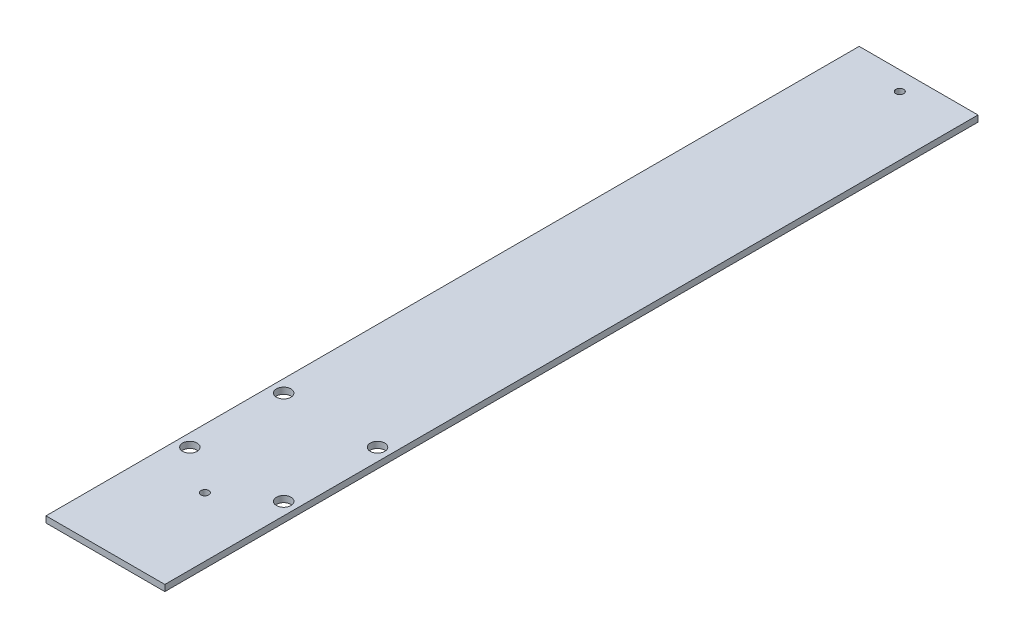
SolidWorks part; units mm, degrees
material "Alloy Steel"
ref_plane "Front" through (0, 0, 0) normal (0, 0, 1) x (1, 0, 0)
ref_plane "Top" through (0, 0, 0) normal (0, 1, 0) x (1, 0, 0)
ref_plane "Right" through (0, 0, 0) normal (1, 0, 0) x (0, 0, -1)
sketch "Sketch1" plane through (0, 0, 0) normal (0, 1, 0) x (1, 0, 0)
  line L1 (0, 0) -> (241.3, 0)
  line L2 (0, 0) -> (0, -1651)
  line L3 (0, -1651) -> (241.3, -1651)
  line L4 (241.3, 0) -> (241.3, -1651)
  dimension "D1" = 241.3
  dimension "D2" = 1651
extrude "Boss-Extrude1" add sketch "Sketch1" along normal blind 12.7
sketch "Sketch2" plane through (0, 12.7, 0) normal (0, 1, 0) x (1, 0, 0)
  line L0 (241.3, 0) -> (0, 0) construction
  line L1 (0, 0) -> (0, -1651) construction
  circle A0 centre (120.65, -38.1) radius 7.9375
  circle A1 centre (120.65, -1449.0573) radius 7.9375
  point P4 (0, 0)
  dimension "D1" = 15.875
  dimension "D2" = 15.875
  dimension "D3" = 1410.9573
  dimension "D4" = 38.1
  dimension "D5" = 120.65
extrude "Cut-Extrude1" cut sketch "Sketch2" against normal through all both and the other way through all
sketch "Sketch3" plane through (0, 0, 0) normal (0, -1, 0) x (1, 0, 0)
  circle A0 centre (215.9, 1193.8) radius 14.7295
  circle A1 centre (25.4, 1193.8) radius 14.7295
  circle A2 centre (25.4, 1384.3) radius 14.7295
  circle A3 centre (215.9, 1384.3) radius 14.7295
extrude "Cut-Extrude2" cut sketch "Sketch3" against normal through all
